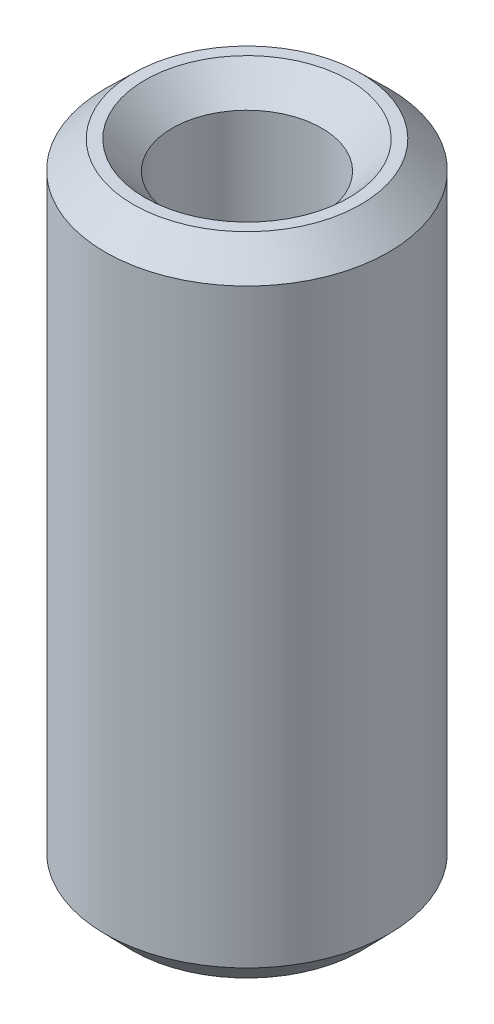
SolidWorks part; units mm, degrees
ref_plane "Front Plane" through (0, 0, 0) normal (0, 0, 1) x (1, 0, 0)
ref_plane "Top Plane" through (0, 0, 0) normal (0, 1, 0) x (1, 0, 0)
ref_plane "Right Plane" through (0, 0, 0) normal (1, 0, 0) x (0, 0, -1)
sketch "Sketch1" plane through (0, 0, 0) normal (0, 1, 0) x (1, 0, 0)
  circle A0 centre (0, 0) radius 12.5
  dimension "SLEEVE_OD" = 25
extrude "Boss-Extrude1" add sketch "Sketch1" along normal blind 56.9574
sketch "Sketch2" plane through (0, 0, 0) normal (0, 1, 0) x (1, 0, 0)
  circle A0 centre (0, 0) radius 6.5875
  dimension "BORE_D" = 13.175
extrude "Cut-Extrude1" cut sketch "Sketch2" along normal through all
chamfer "Chamfer1" distance 2.4065 angle 45.734 4 edges at (0, 56.9574, 6.5875) (0, 0, 6.5875) (0, 0, 12.5) (0, 56.9574, 12.5) first distance on face at (0, 56.9574, 6.5875) first distance on face at (0, 0, 6.5875) first distance on face at (0, 56.9574, 12.5)
